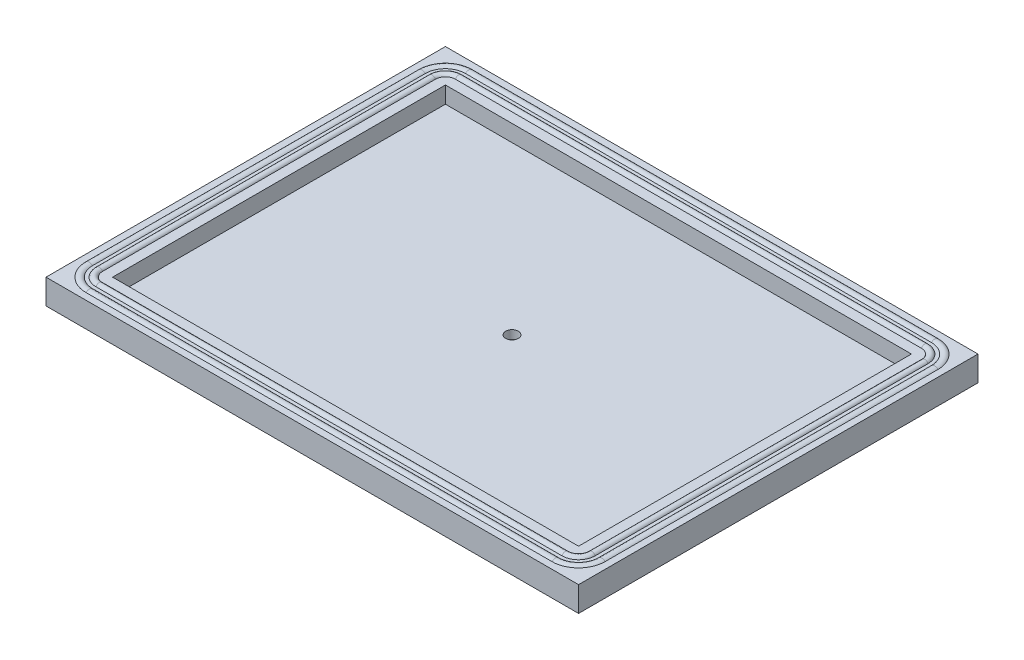
SolidWorks part; units mm, degrees
ref_plane "Front Plane" through (0, 0, 0) normal (0, 0, 1) x (1, 0, 0)
ref_plane "Top Plane" through (0, 0, 0) normal (0, 1, 0) x (1, 0, 0)
ref_plane "Right Plane" through (0, 0, 0) normal (1, 0, 0) x (0, 0, -1)
sketch "Sketch1" plane through (0, 0, 0) normal (0, 1, 0) x (1, 0, 0)
  line L12 (71.4455, 53.0596) -> (71.4455, -99.3404)
  line L13 (71.4455, -99.3404) -> (274.6455, -99.3404)
  line L14 (274.6455, -99.3404) -> (274.6455, 53.0596)
  line L15 (274.6455, 53.0596) -> (71.4455, 53.0596)
  dimension "D1" = 203.2
  dimension "D2" = 152.4
extrude "main body" add sketch "Sketch1" along normal blind 9.525
sketch "Sketch2" plane through (0, 9.525, 0) normal (0, 1, 0) x (1, 0, 0)
  line L0 (173.0455, 53.0596) -> (173.0455, 24.7212) construction
  line L1 (274.6455, 53.0596) -> (71.4455, 53.0596) construction
  line L2 (71.4455, -23.1404) -> (118.1145, -23.1404) construction
  line L3 (71.4455, 53.0596) -> (71.4455, -99.3404) construction
  line L4 (261.9455, -86.6404) -> (84.1455, -86.6404)
  line L5 (84.1455, -86.6404) -> (84.1455, 40.3596)
  line L6 (261.9455, -86.6404) -> (261.9455, 40.3596)
  line L7 (261.9455, 40.3596) -> (84.1455, 40.3596)
  line L8 (84.1455, 40.3596) -> (261.9455, -86.6404) construction
  line L9 (274.6455, -99.3404) -> (274.6455, 53.0596) construction
  line L10 (71.4455, -99.3404) -> (274.6455, -99.3404) construction
  point P11 (173.0455, 40.3596)
  point P13 (173.0455, -86.6404)
  point P14 (261.9455, -23.1404)
  point P15 (84.1455, -23.1404)
  dimension "D1" = 12.7
  dimension "D2" = 12.7
extrude "slide inset" cut sketch "Sketch2" against normal offset from surface (6.35 mm away) 3.175 up to face at (173.0455, 0, 23.1404)
sketch "offset rounded from slide" plane through (0, 9.525, 0) normal (0, 1, 0) x (1, 0, 0)
  line L8 (264.4855, -89.1804) -> (264.4855, 42.8996)
  line L9 (81.6055, -89.1804) -> (264.4855, -89.1804)
  line L10 (81.6055, 42.8996) -> (81.6055, -89.1804)
  line L11 (264.4855, 42.8996) -> (81.6055, 42.8996)
  line L12 (264.4855, -86.6404) -> (264.4855, 40.3596)
  line L13 (84.1455, -89.1804) -> (261.9455, -89.1804)
  line L14 (81.6055, 40.3596) -> (81.6055, -86.6404)
  line L15 (261.9455, 42.8996) -> (84.1455, 42.8996)
  arc A0 (84.1455, -89.1804) -> (81.6055, -86.6404) centre (84.1455, -86.6404) cw
  arc A1 (264.4855, -86.6404) -> (261.9455, -89.1804) centre (261.9455, -86.6404) cw
  arc A2 (264.4855, 40.3596) -> (261.9455, 42.8996) centre (261.9455, 40.3596) ccw
  arc A3 (81.6055, 40.3596) -> (84.1455, 42.8996) centre (84.1455, 40.3596) cw
  dimension "D2" = 2.54
  dimension "D1" = 2.54
sketch "gasket bump profiles" plane through (0, 9.525, 0) normal (0, 1, 0) x (1, 0, 0)
  line L8 (79.0655, 40.3596) -> (79.0655, -86.6404)
  line L9 (84.1455, -91.7204) -> (261.9455, -91.7204)
  line L10 (267.0255, -86.6404) -> (267.0255, 40.3596)
  line L11 (261.9455, 45.4396) -> (84.1455, 45.4396)
  line L12 (79.0655, 40.3596) -> (79.0655, -86.6404)
  line L13 (84.1455, -91.7204) -> (261.9455, -91.7204)
  line L14 (267.0255, -86.6404) -> (267.0255, 40.3596)
  line L15 (261.9455, 45.4396) -> (84.1455, 45.4396)
  arc A8 (79.0655, -86.6404) -> (84.1455, -91.7204) centre (84.1455, -86.6404) ccw
  arc A9 (261.9455, -91.7204) -> (267.0255, -86.6404) centre (261.9455, -86.6404) ccw
  arc A10 (267.0255, 40.3596) -> (261.9455, 45.4396) centre (261.9455, 40.3596) ccw
  arc A11 (84.1455, 45.4396) -> (79.0655, 40.3596) centre (84.1455, 40.3596) ccw
  arc A16 (79.0655, -86.6404) -> (84.1455, -91.7204) centre (84.1455, -86.6404) ccw
  arc A17 (261.9455, -91.7204) -> (267.0255, -86.6404) centre (261.9455, -86.6404) ccw
  arc A18 (267.0255, 40.3596) -> (261.9455, 45.4396) centre (261.9455, 40.3596) ccw
  arc A19 (84.1455, 45.4396) -> (79.0655, 40.3596) centre (84.1455, 40.3596) ccw
  dimension "D1" = 2.54
ref_plane "Plane1 for gasket bump shape" through (0, 0, 23.1404) normal (0, 0, -1) x (-1, 0, 0)
sketch "gasket bump shape" plane through (0, 0, 23.1404) normal (0, 0, -1) x (-1, 0, 0)
  line L0 (-79.0655, 9.525) -> (-79.0655, 13.8205) construction
  line L1 (-77.7955, 9.525) -> (-80.3355, 9.525)
  line L2 (-79.0655, 10.3187) -> (-89.9155, 10.3187) construction
  line L3 (-79.0655, 9.525) -> (-75.2555, 9.525) construction
  line L4 (-77.1605, 9.525) -> (-77.1605, 13.8205) construction
  line L5 (-76.5255, 9.525) -> (-73.9855, 9.525)
  line L6 (-75.2555, 10.033) -> (-81.1283, 10.033) construction
  line L8 (-274.6455, 9.525) -> (-71.4455, 9.525) construction
  arc A0 (-77.7955, 9.525) -> (-80.3355, 9.525) centre (-79.0655, 8.9059) ccw
  arc A1 (-76.5255, 9.525) -> (-73.9855, 9.525) centre (-75.2555, 8.1915) cw
  dimension "D1" = 0.7937
  dimension "D2" = 2.54
  dimension "D3" = 3.81
  dimension "D4" = 0.508
sweep "Sweep for sealing ribs" add profiles "gasket bump shape" path "gasket bump profiles"
hole_wizard "#10-32 Tapped Hole2" positions "Sketch26" profile "Sketch27" tap size "#10-32" standard "ANSI Inch" end condition through all
sketch "Sketch26" plane through (0, 0, 0) normal (0, -1, 0) x (1, 0, 0)
  line L0 (71.4455, 99.3404) -> (274.6455, 99.3404) construction
  line L1 (71.4455, -53.0596) -> (71.4455, 99.3404) construction
  point P0 (173.0455, 23.1404)
  point P4 (173.0455, 99.3404)
  point P7 (71.4455, 23.1404)
sketch "Sketch27" plane through (173.0455, 0, 23.1404) normal (1, 0, 0) x (0, 0, -1)
  line L0 (0, 0) -> (0, 10.3187)
  line L1 (0, 10.3187) -> (2.413, 10.3187)
  line L2 (2.413, 10.3187) -> (2.413, 0)
  line L5 (2.413, 0) -> (0, 0)
  line L11 (0, -6.35) -> (0, 107.95) construction
  dimension "Thread Major Dia." = 4.826
  dimension "Thru Tap Drill Depth" = 10.3187
equation "\"BodyLength\"=8"
equation "\"BodyWidth\"=6"
equation "\"D2@Sketch1\"=\"BodyWidth\""
equation "\"D1@Sketch1\"= \"BodyLength\""
equation "\"SealingEdge\"=0.5"
equation "\"D1@Sketch2\"=\"SealingEdge\""
equation "\"D2@Sketch2\"=\"SealingEdge\""
